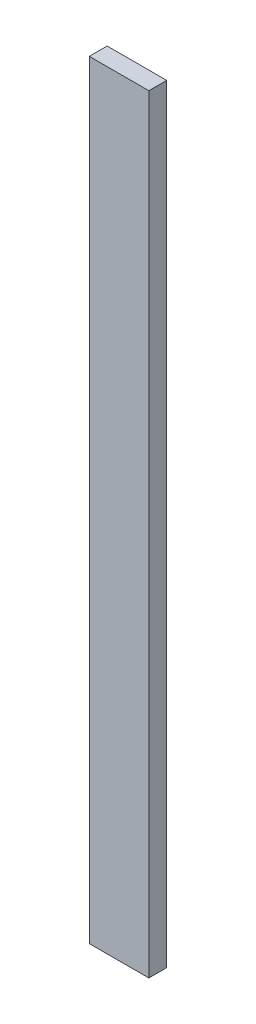
SolidWorks part; units mm, degrees
material "Pine"
ref_plane "Front Plane" through (0, 0, 0) normal (0, 0, 1) x (1, 0, 0)
ref_plane "Top Plane" through (0, 0, 0) normal (0, 1, 0) x (1, 0, 0)
ref_plane "Right Plane" through (0, 0, 0) normal (1, 0, 0) x (0, 0, -1)
sketch "Sketch1" plane through (0, 0, 0) normal (0, 0, 1) x (1, 0, 0)
  line L0 (-49.142, 787.7748) -> (-49.142, -31.3752)
  line L1 (-49.142, -31.3752) -> (14.358, -31.3752)
  line L2 (-49.142, 787.7748) -> (14.358, 787.7748)
  line L3 (14.358, -31.3752) -> (14.358, 787.7748)
extrude "Boss-Extrude1" add sketch "Sketch1" along normal blind 19.05
